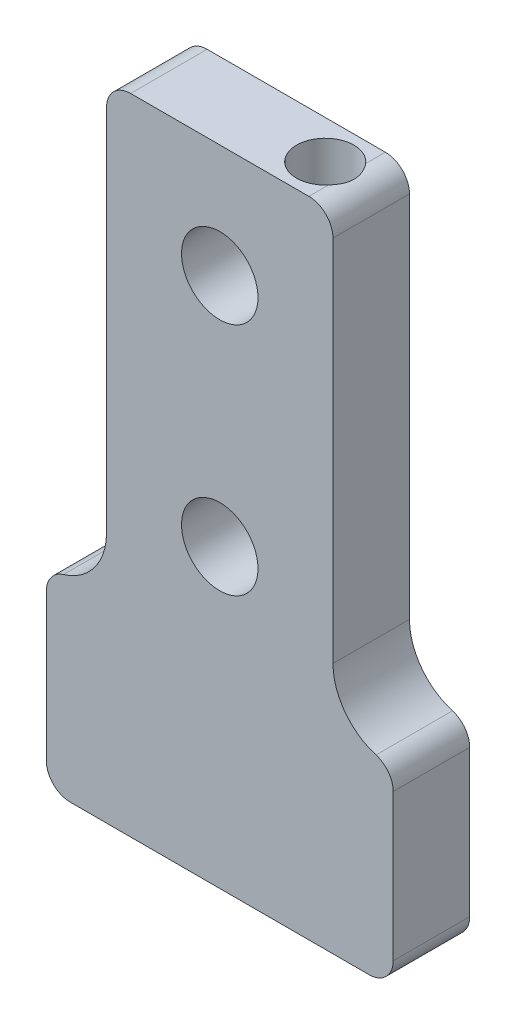
SolidWorks part; units mm, degrees
ref_plane "Front" through (0, 0, 0) normal (0, 0, 1) x (1, 0, 0)
ref_plane "Top" through (0, 0, 0) normal (0, 1, 0) x (1, 0, 0)
ref_plane "Right" through (0, 0, 0) normal (1, 0, 0) x (0, 0, -1)
ref_axis "side-side" through (80.9, 0, 0) along (-1, 0, 0)
ref_axis "up-down" through (0, 50, 0) along (0, -1, 0)
ref_axis "front-back" through (0, 0, -80.9) along (0, 0, 1)
sketch "Sketch1" plane through (0, 0, 0) normal (0, 0, 1) x (1, 0, 0)
  line L0 (9.398, -3.7) -> (9.398, 0) construction
  line L1 (-9.398, -3.7) -> (-9.398, 0) construction
  line L2 (9.398, -3.7) -> (9.398, 28.878)
  line L3 (-9.398, -3.7) -> (-9.398, 28.878)
  line L4 (-14.398, -8.7) -> (-14.398, -24.575)
  line L5 (-41.275, -24.575) -> (41.275, -24.575) construction
  line L6 (-14.398, -24.575) -> (14.398, -24.575)
  line L7 (14.398, -24.575) -> (14.398, -8.7)
  line L9 (-9.398, 28.878) -> (9.398, 28.878)
  arc A0 (-14.398, -8.7) -> (-9.398, -3.7) centre (-14.398, -3.7) ccw construction
  arc A1 (9.398, -3.7) -> (14.398, -8.7) centre (14.398, -3.7) ccw construction
  arc A2 (9.398, -3.7) -> (14.398, -8.7) centre (14.398, -3.7) ccw
  arc A3 (-14.398, -8.7) -> (-9.398, -3.7) centre (-14.398, -3.7) ccw
  circle A5 centre (0, 0) radius 3.175 construction
  circle A6 centre (0, 0) radius 3.175
  circle A7 centre (0, 19.48) radius 3.175
  arc A8 (-8.815, 22.7385) -> (8.1024, 24.2417) centre (0, 19.48) cw construction
  point P19 (-7.9375, 28.3025)
  point P20 (0, 0)
  dimension "D1" = 28.18
extrude "Boss-Extrude1" add sketch "Sketch1" against normal blind 6.35
sketch "Sketch2" plane through (0, 28.878, 0) normal (0, 1, 0) x (1, 0, 0)
  line L0 (9.398, 0) -> (-9.398, 0) construction
  line L2 (3.2, -2.4915) -> (3.2, 18.2469) construction
  line L3 (9.3912, -2.0403) -> (9.3912, 10.6478) construction
  line L4 (0, -50) -> (0, 50) construction
  circle A0 centre (5.5812, 3.175) radius 2.3813
  dimension "D1" = 4.7625
  dimension "D3" = 3.81
  dimension "D2" = 3.175
  dimension "D4" = 3.2
  dimension "D5" = 9.3912
extrude "Cut-Extrude2" cut sketch "Sketch2" against normal through all
fillet "Fillet1" radius 2 6 edges at (14.398, -8.7, -3.175) (9.398, 28.878, -3.175) (-14.398, -8.7, -3.175) (-9.398, 28.878, -3.175) (14.398, -24.575, -3.175) (-14.398, -24.575, -3.175)
